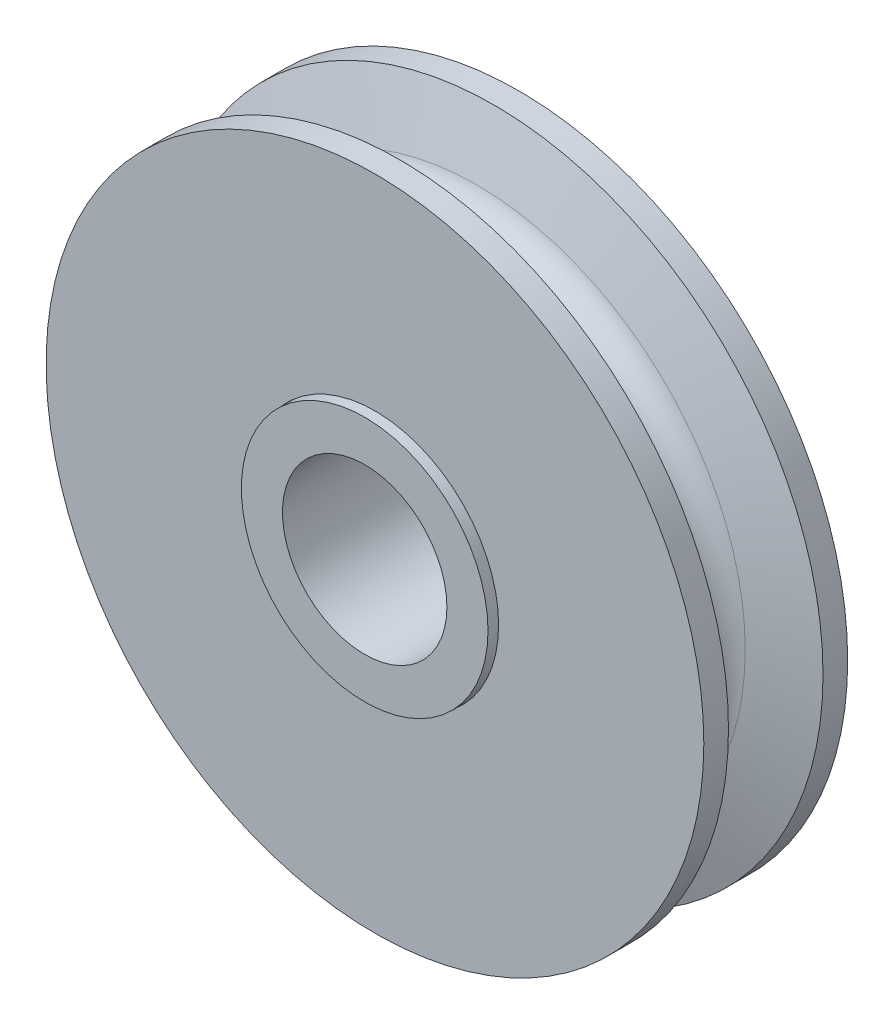
SolidWorks part; units mm, degrees
ref_plane "Front" through (0, 0, 0) normal (0, 0, 1) x (1, 0, 0)
ref_plane "Top" through (0, 0, 0) normal (0, 1, 0) x (1, 0, 0)
ref_plane "Right" through (0, 0, 0) normal (1, 0, 0) x (0, 0, -1)
sketch "Sketch1" plane through (0, 0, 0) normal (1, 0, 0) x (0, 0, -1)
  line L0 (3.6513, 25.4) -> (5.5562, 25.4)
  line L1 (-3.6512, 25.4) -> (-5.5562, 25.4)
  line L2 (-3.6512, 25.4) -> (-2.2842, 20.7585)
  line L4 (6.35, 6.35) -> (-6.35, 6.35)
  line L6 (3.6513, 25.4) -> (2.2842, 20.7585)
  line L8 (-6.35, 0) -> (6.35, 0) construction
  line L9 (-5.5562, 9.525) -> (-5.5562, 25.4)
  line L10 (5.5562, 25.4) -> (5.5563, 9.525)
  line L12 (-5.5562, 9.525) -> (-6.35, 9.525)
  line L13 (-6.35, 9.525) -> (-6.35, 6.35)
  line L14 (0, 19.05) -> (0, -19.05) construction
  line L15 (6.35, 9.525) -> (5.5563, 9.525)
  line L16 (6.35, 9.525) -> (6.35, 6.35)
  line L17 (-5.5562, 25.4) -> (-5.5562, -25.4) construction
  arc A0 (-2.2842, 20.7585) -> (2.2842, 20.7585) centre (0, 21.4312) ccw
  circle A1 centre (0, 21.4312) radius 2.3813 construction
  circle A2 centre (0, 0) radius 6.35 construction
  circle A3 centre (0, 0) radius 9.525 construction
  circle A4 centre (0, 0) radius 15.875 construction
  circle A5 centre (0, -21.4313) radius 2.3812 construction
  point P28 (-5.5562, 0)
  dimension "Rope Dia" = 4.7625
  dimension "Shaft Dia" = 12.7
  dimension "D1" = 19.05
  dimension "D3" = 31.75
  dimension "Wd" = 12.7
  dimension "D8" = 1.905
  dimension "Groove Dia" = 38.1
  dimension "OD" = 50.8
  dimension "w Wd" = 11.1125
revolve "Revolve1" add sketch "Sketch1" angle 360 about L8
sketch "Sketch2" plane through (0, 0, 0) normal (0, 0, 1) x (1, 0, 0)
  circle A0 centre (0, 0) radius 9.525 construction
  circle A1 centre (0, 0) radius 9.525
extrude "Cut-Extrude-Thin1" cut sketch "Sketch2" against normal through all and the other way through all thin thin type one direction wall 0.0254
equation "\"D8@Sketch1\" = \"Wd@Sketch1\" * .15"
equation "\"D1@Sketch1\" = \"Shaft Dia@Sketch1\" * 1.5"
equation "\"D3@Sketch1\" = \"Shaft Dia@Sketch1\" * 2.5"
